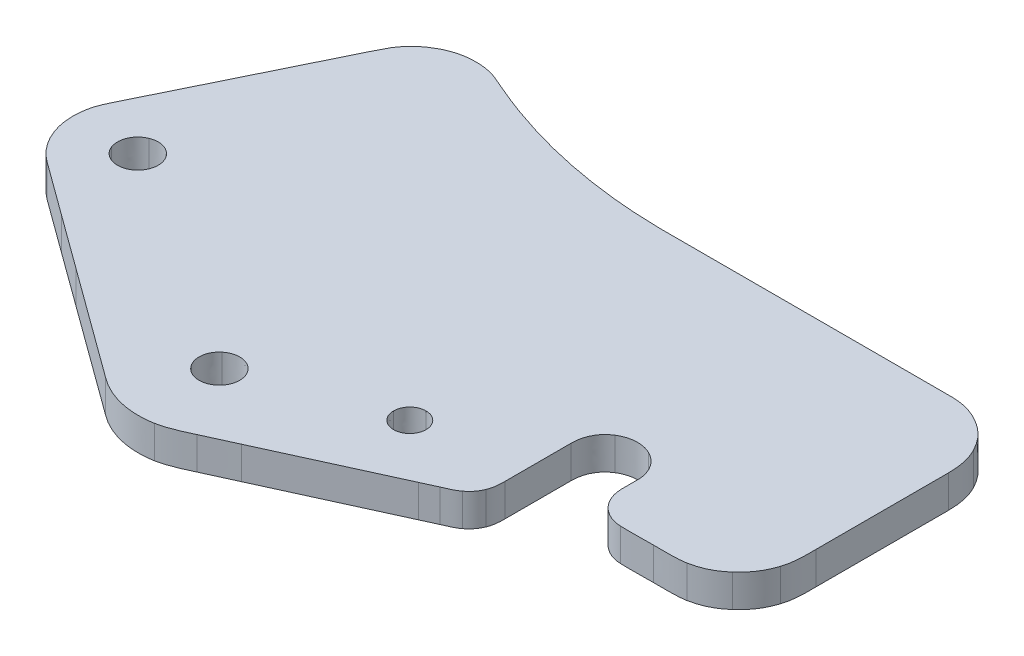
SolidWorks part; units mm, degrees
ref_plane "Front Plane" through (0, 0, 0) normal (0, 0, 1) x (1, 0, 0)
ref_plane "Top Plane" through (0, 0, 0) normal (0, 1, 0) x (1, 0, 0)
ref_plane "Right Plane" through (0, 0, 0) normal (1, 0, 0) x (0, 0, -1)
sketch "Imported Profile" plane through (0, 0, 0) normal (0, 1, 0) x (1, 0, 0)
  spline S0 degree 3 poles (47.6488, 3.4753) (40.593, 8.6202) (33.5375, 13.7602) (26.4819, 18.9072) knots 0 0 0 0 1 1 1 1
  spline S1 degree 3 poles (26.4819, 18.9072) (22.961, 21.4772) (19.4332, 24.0473) (15.9054, 26.6173) knots 0 0 0 0 1 1 1 1
  spline S2 degree 3 poles (15.9054, 26.6173) (12.3776, 29.1943) (8.8292, 31.7229) (5.329, 34.3343) knots 0 0 0 0 1 1 1 1
  spline S3 degree 3 poles (5.329, 34.3343) (1.7254, 37.0215) (-0.1832, 41.3968) (0.2923, 45.8616) knots 0 0 0 0 1 1 1 1
  spline S4 degree 3 poles (0.2923, 45.8616) (0.5679, 48.4454) (1.3534, 49.7752) (2.4489, 52.0214) knots 0 0 0 0 1 1 1 1
  spline S5 degree 3 poles (2.4489, 52.0214) (3.4066, 53.9851) (4.3713, 55.942) (5.329, 57.8988) knots 0 0 0 0 1 1 1 1
  spline S6 degree 3 poles (5.329, 57.8988) (9.1599, 65.7398) (12.9978, 73.5809) (16.8287, 81.4288) knots 0 0 0 0 1 1 1 1
  spline S7 degree 3 poles (16.8287, 81.4288) (17.2628, 82.3038) (19.1783, 86.3001) (19.7019, 87.1339) knots 0 0 0 0 1 1 1 1
  spline S8 degree 3 poles (19.7019, 87.1339) (20.9491, 89.1182) (22.4649, 90.5238) (24.532, 91.6194) knots 0 0 0 0 1 1 1 1
  spline S9 degree 3 poles (24.532, 91.6194) (26.6886, 92.7563) (28.7694, 93.2041) (31.2086, 93.0595) knots 0 0 0 0 1 1 1 1
  spline S10 degree 3 poles (31.2086, 93.0595) (33.8062, 92.9079) (34.9913, 92.2395) (37.2926, 91.2473) knots 0 0 0 0 1 1 1 1
  spline S11 degree 3 poles (37.2926, 91.2473) (45.3403, 87.754) (53.5052, 85.3975) (62.18, 84.0608) knots 0 0 0 0 1 1 1 1
  spline S12 degree 3 poles (62.18, 84.0608) (71.9503, 82.5519) (78.5373, 82.8688) (88.3283, 82.8688) knots 0 0 0 0 1 1 1 1
  spline S13 degree 3 poles (88.3283, 82.8688) (97.065, 82.8688) (105.8018, 82.8688) (114.5317, 82.8688) knots 0 0 0 0 1 1 1 1
  spline S14 degree 3 poles (114.5317, 82.8688) (118.8518, 82.8688) (123.1719, 82.8688) (127.499, 82.8688) knots 0 0 0 0 1 1 1 1
  spline S15 degree 3 poles (127.499, 82.8688) (129.6487, 82.8688) (131.7985, 82.9378) (133.9413, 82.8638) knots 0 0 0 0 1 1 1 1
  spline S16 degree 3 poles (133.9413, 82.8638) (136.2426, 82.7813) (138.1926, 82.1886) (140.1494, 80.9759) knots 0 0 0 0 1 1 1 1
  spline S17 degree 3 poles (140.1494, 80.9759) (142.244, 79.6874) (143.6978, 78.1096) (144.8071, 75.9116) knots 0 0 0 0 1 1 1 1
  spline S18 degree 3 poles (144.8071, 75.9116) (145.8338, 73.8928) (146.1783, 71.8946) (146.1783, 69.6692) knots 0 0 0 0 1 1 1 1
  spline S19 degree 3 poles (146.1783, 69.6692) (146.1783, 65.3489) (146.1783, 61.022) (146.1783, 56.7017) knots 0 0 0 0 1 1 1 1
  spline S20 degree 3 poles (146.1783, 56.7017) (146.1783, 52.3954) (146.1783, 48.089) (146.1783, 43.7827) knots 0 0 0 0 1 1 1 1
  spline S21 degree 3 poles (146.1783, 43.7827) (146.1783, 41.6536) (146.2543, 39.5865) (145.5788, 37.485) knots 0 0 0 0 1 1 1 1
  spline S22 degree 3 poles (145.5788, 37.485) (144.8416, 35.1768) (143.6909, 33.4061) (141.865, 31.8006) knots 0 0 0 0 1 1 1 1
  spline S23 degree 3 poles (141.865, 31.8006) (140.0805, 30.2296) (138.2063, 29.3133) (135.8637, 28.8654) knots 0 0 0 0 1 1 1 1
  spline S24 degree 3 poles (135.8637, 28.8654) (134.2514, 28.5624) (131.137, 28.6449) (129.5247, 28.6449) knots 0 0 0 0 1 1 1 1
  spline S25 degree 3 poles (129.5247, 28.6449) (127.3818, 28.6449) (125.2321, 28.5624) (123.0893, 28.6449) knots 0 0 0 0 1 1 1 1
  spline S26 degree 3 poles (123.0893, 28.6449) (120.7879, 28.7344) (118.714, 30.0574) (117.6736, 32.1107) knots 0 0 0 0 1 1 1 1
  spline S27 degree 3 poles (117.6736, 32.1107) (116.5849, 34.2328) (117.0741, 36.3137) (116.9708, 38.4427) knots 0 0 0 0 1 1 1 1
  spline S28 degree 3 poles (116.9708, 38.4427) (116.8538, 40.751) (115.5032, 42.8042) (113.4292, 43.824) knots 0 0 0 0 1 1 1 1
  spline S29 degree 3 poles (113.4292, 43.824) (111.4448, 44.8024) (109.1022, 44.6715) (107.2349, 43.4935) knots 0 0 0 0 1 1 1 1
  spline S30 degree 3 poles (107.2349, 43.4935) (105.1885, 42.1981) (104.279, 40.1655) (104.279, 37.8228) knots 0 0 0 0 1 1 1 1
  spline S31 degree 3 poles (104.279, 37.8228) (104.279, 33.5096) (104.279, 29.1963) (104.279, 24.8762) knots 0 0 0 0 1 1 1 1
  spline S32 degree 3 poles (104.279, 24.8762) (104.279, 23.7806) (104.224, 22.7471) (103.79, 21.6998) knots 0 0 0 0 1 1 1 1
  spline S33 degree 3 poles (103.79, 21.6998) (103.335, 20.618) (102.7014, 19.7981) (101.7643, 19.0884) knots 0 0 0 0 1 1 1 1
  spline S34 degree 3 poles (101.7643, 19.0884) (100.8824, 18.4201) (99.8833, 18.0618) (98.9049, 17.6208) knots 0 0 0 0 1 1 1 1
  spline S35 degree 3 poles (98.9049, 17.6208) (97.9265, 17.1728) (96.9481, 16.7251) (95.9628, 16.2772) knots 0 0 0 0 1 1 1 1
  spline S36 degree 3 poles (95.9628, 16.2772) (88.046, 12.6668) (80.1291, 9.0563) (72.2054, 5.4458) knots 0 0 0 0 1 1 1 1
  spline S37 degree 3 poles (72.2054, 5.4458) (70.2279, 4.5501) (68.2504, 3.6475) (66.2729, 2.7449) knots 0 0 0 0 1 1 1 1
  spline S38 degree 3 poles (66.2729, 2.7449) (64.2955, 1.8423) (62.3869, 0.8983) (60.2027, 0.4918) knots 0 0 0 0 1 1 1 1
  spline S39 degree 3 poles (60.2027, 0.4918) (55.7792, -0.335) (51.2248, 0.7468) (47.6488, 3.4753) knots 0 0 0 0 1 1 1 1
  spline S40 degree 3 poles (87.8115, 25.9559) (87.8115, 27.706) (86.3921, 29.1253) (84.6351, 29.1253) knots 0 0 0 0 1 1 1 1
  spline S41 degree 3 poles (84.6351, 29.1253) (82.8781, 29.1253) (81.4587, 27.706) (81.4587, 25.9559) knots 0 0 0 0 1 1 1 1
  spline S42 degree 3 poles (81.4587, 25.9559) (81.4587, 24.1988) (82.8781, 22.7795) (84.6351, 22.7795) knots 0 0 0 0 1 1 1 1
  spline S43 degree 3 poles (84.6351, 22.7795) (86.3921, 22.7795) (87.8115, 24.1988) (87.8115, 25.9559) knots 0 0 0 0 1 1 1 1
  spline S44 degree 3 poles (16.5876, 46.0339) (15.747, 48.0596) (13.425, 49.0242) (11.3993, 48.1836) knots 0 0 0 0 1 1 1 1
  spline S45 degree 3 poles (11.3993, 48.1836) (9.3735, 47.343) (8.4158, 45.021) (9.2495, 42.9953) knots 0 0 0 0 1 1 1 1
  spline S46 degree 3 poles (9.2495, 42.9953) (10.0901, 40.9696) (12.4121, 40.0118) (14.4378, 40.8455) knots 0 0 0 0 1 1 1 1
  spline S47 degree 3 poles (14.4378, 40.8455) (16.4635, 41.6862) (17.4213, 44.0081) (16.5876, 46.0339) knots 0 0 0 0 1 1 1 1
  spline S48 degree 3 poles (60.32, 18.6385) (58.914, 20.3197) (56.4129, 20.5402) (54.7317, 19.1275) knots 0 0 0 0 1 1 1 1
  spline S49 degree 3 poles (54.7317, 19.1275) (53.0505, 17.7219) (52.83, 15.2207) (54.2427, 13.5395) knots 0 0 0 0 1 1 1 1
  spline S50 degree 3 poles (54.2427, 13.5395) (55.6552, 11.8583) (58.1563, 11.6447) (59.8375, 13.0505) knots 0 0 0 0 1 1 1 1
  spline S51 degree 3 poles (59.8375, 13.0505) (61.5118, 14.4561) (61.7323, 16.9642) (60.32, 18.6385) knots 0 0 0 0 1 1 1 1
extrude "Boss-Extrude1" add sketch "Imported Profile" along normal blind 6.35
